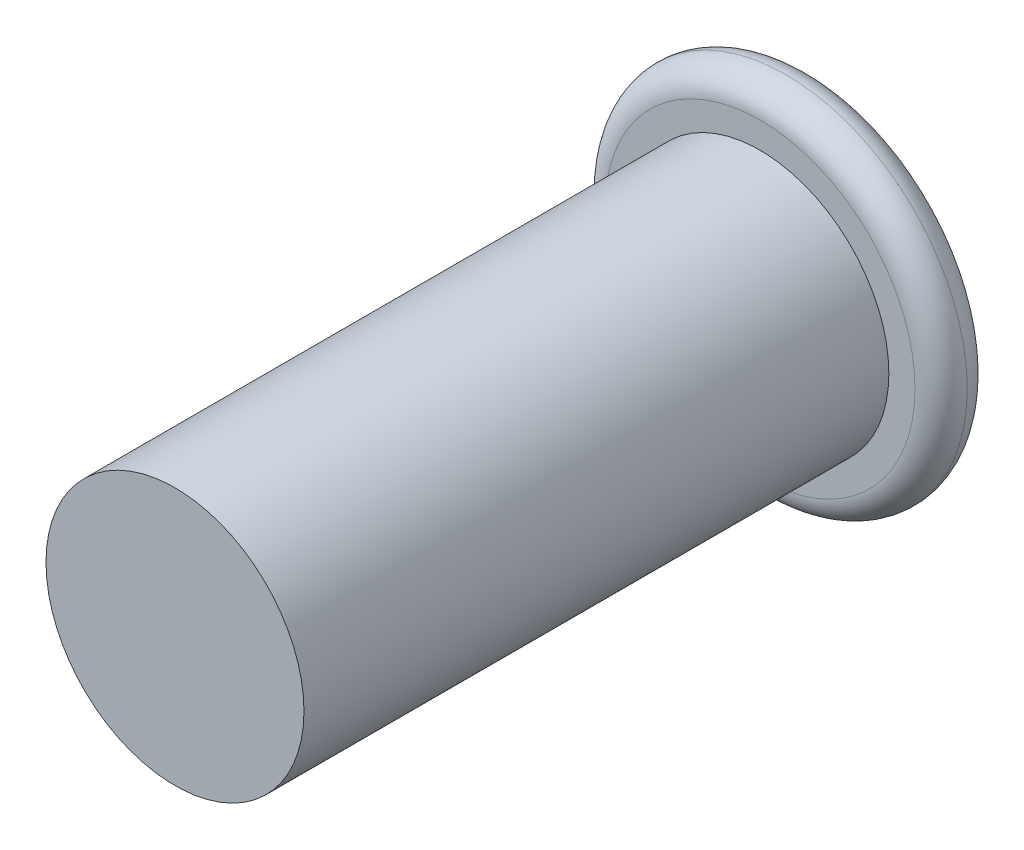
SolidWorks part; units mm, degrees
material "AISI 304"
ref_plane "Front Plane" through (0, 0, 0) normal (0, 0, 1) x (1, 0, 0)
ref_plane "Top Plane" through (0, 0, 0) normal (0, 1, 0) x (1, 0, 0)
ref_plane "Right Plane" through (0, 0, 0) normal (1, 0, 0) x (0, 0, -1)
sketch "Sketch1" plane through (0, 0, 0) normal (0, 0, 1) x (1, 0, 0)
  circle A0 centre (0, 0) radius 1.235
  dimension "D1" = 2.47
extrude "Boss-Extrude1" add sketch "Sketch1" along normal blind 5.6
sketch "Sketch2" plane through (0, 0, 0) normal (0, 0, -1) x (-1, 0, 0)
  circle A0 centre (0, 0) radius 1.735
  dimension "D1" = 3.47
extrude "Boss-Extrude2" add sketch "Sketch2" along normal blind 0.5
fillet "Fillet1" radius 0.25 2 edges at (-1.735, 0, 0) (-1.735, 0, -0.5)
